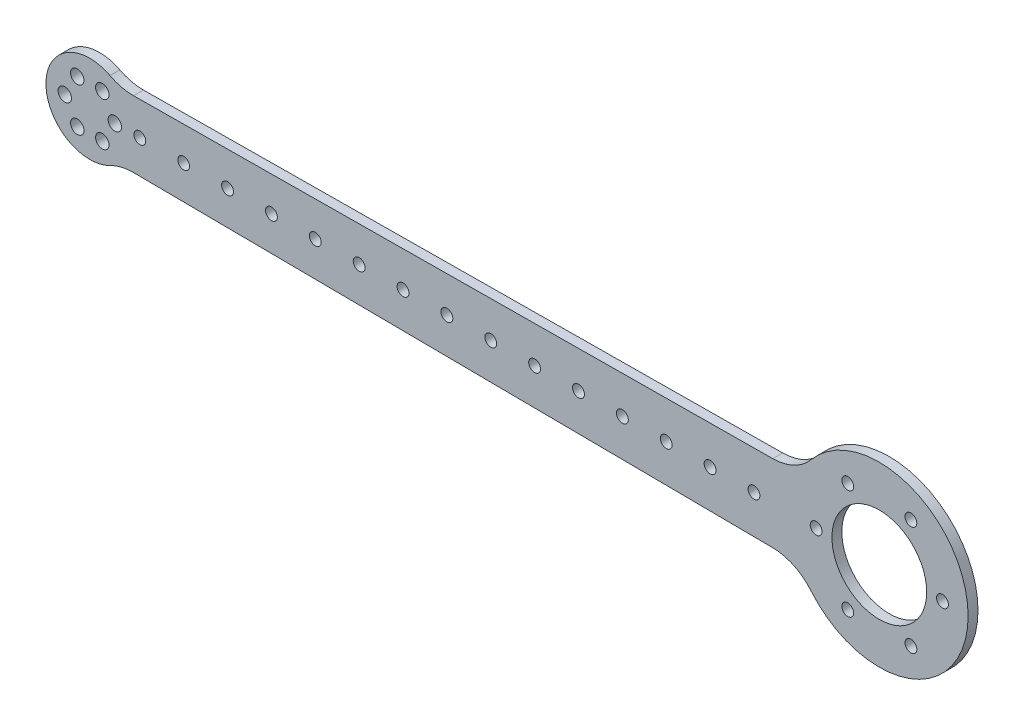
SolidWorks part; units mm, degrees
material "Hexcel AS4C (3000 Filaments)"
ref_plane "Front Plane" through (0, 0, 0) normal (0, 0, 1) x (1, 0, 0)
ref_plane "Top Plane" through (0, 0, 0) normal (0, 1, 0) x (1, 0, 0)
ref_plane "Right Plane" through (0, 0, 0) normal (1, 0, 0) x (0, 0, -1)
sketch "Sketch1" plane through (0, 0, 0) normal (0, 0, 1) x (1, 0, 0)
  line L0 (-100, 0) -> (100, 0) construction
  line L1 (-88.9892, 1.5) -> (77.6857, 2.8851)
  line L2 (-92.7234, 8.3988) -> (79.762, 9.8322)
  line L3 (-88.9892, -1.5) -> (77.6857, -2.8851)
  line L4 (-92.7234, -8.3988) -> (79.762, -9.8322)
  line L5 (-100, 0) -> (-100.0693, -8.3377) construction
  line L6 (-100.0693, -8.3377) -> (-92.7234, -8.3988) construction
  line L7 (-92.7234, 8.3988) -> (-100.0693, 8.3377) construction
  line L8 (-100.0693, 8.3377) -> (-100, 0) construction
  line L9 (-88.9892, 1.5) -> (-88.9892, -1.5)
  line L10 (100, 0) -> (99.9169, -9.9997) construction
  line L11 (99.9169, -9.9997) -> (79.762, -9.8322) construction
  line L12 (79.762, 9.8322) -> (99.9169, 9.9997) construction
  line L13 (99.9169, 9.9997) -> (100, 0) construction
  circle A0 centre (-100, 0) radius 11.1125 construction
  circle A1 centre (100, 0) radius 22.5 construction
  arc A2 (79.762, 9.8322) -> (79.762, -9.8322) centre (100, 0) cw
  arc A3 (77.6857, 2.8851) -> (77.6857, -2.8851) centre (100, 0) ccw
  arc A4 (-92.7234, 8.3988) -> (-92.7234, -8.3988) centre (-100, 0) ccw
  point P4 (0, 0)
  point P23 (-88.9892, 0)
  dimension "D2" = 22.225
  dimension "D3" = 45
  dimension "D1" = 200
  dimension "D5" = 6.9296
  dimension "D6" = 10
  dimension "D7" = 6.9296
  dimension "D4" = 10
  dimension "D8" = 3
extrude "Boss-Extrude1" add sketch "Sketch1" along normal mid plane 2.5
fillet "Fillet1" radius 12.7 4 edges at (79.762, 9.8322, 0) (79.762, -9.8322, 0) (-92.7234, -8.3988, 0) (-92.7234, 8.3988, 0)
sketch "Sketch2" plane through (0, 0, 0) normal (0, 0, 1) x (1, 0, 0)
  line L8 (-88.9892, 1.5) -> (-88.9892, -1.5) construction
  line L9 (-88.9892, -1.5) -> (77.6857, -2.8851) construction
  line L10 (77.6857, 2.8851) -> (-88.9892, 1.5) construction
  line L12 (-88.9892, 1.5) -> (-88.9892, -1.5)
  line L13 (-88.9892, -1.5) -> (77.6857, -2.8851)
  line L14 (77.6857, 2.8851) -> (-88.9892, 1.5)
  arc A6 (77.6857, 2.8851) -> (77.6857, -2.8851) centre (100, 0) ccw construction
  arc A7 (77.6857, 2.8851) -> (77.6857, -2.8851) centre (100, 0) ccw
extrude "Boss-Extrude2" add sketch "Sketch2" along normal mid plane 2.5
ref_axis "Axis1" through (100, 0, 1.25) along (0, 0, -1)
ref_axis "Axis2" through (-100, 0, 1.25) along (0, 0, -1)
sketch "Sketch3" plane through (0, 0, 0) normal (0, 0, 1) x (1, 0, 0)
  circle A0 centre (100, 0) radius 12
  dimension "D1" = 24
extrude "Cut-Extrude1" cut sketch "Sketch3" against normal through all both and the other way through all
sketch "Sketch5" plane through (0, 0, 0) normal (0, 0, 1) x (1, 0, 0)
  line L0 (100, 0) -> (116, 0) construction
  circle A0 centre (116, 0) radius 1.5
  dimension "D2" = 3
  dimension "D1" = 16
extrude "Cut-Extrude2" cut sketch "Sketch5" against normal through all both and the other way through all
pattern_circular "CirPattern1" count 6 over 360 about axis through (100, 0, 1.25) along (0, 0, -1) of "Cut-Extrude2"
sketch "Sketch6" plane through (0, 0, 1.25) normal (0, 0, 1) x (1, 0, 0)
  line L0 (100, 0) -> (68.25, 0) construction
  line L1 (-100, 0) -> (-31.7625, 0) construction
  circle A0 centre (68.25, 0) radius 1.5
  circle A1 centre (57.1375, 0) radius 1.5
  circle A2 centre (46.025, 0) radius 1.5
  circle A3 centre (34.9125, 0) radius 1.5
  circle A4 centre (23.8, 0) radius 1.5
  circle A5 centre (12.6875, 0) radius 1.5
  circle A6 centre (1.575, 0) radius 1.5
  circle A7 centre (-9.5375, 0) radius 1.5
  circle A8 centre (-20.65, 0) radius 1.5
  circle A9 centre (-31.7625, 0) radius 1.5
  circle A10 centre (-42.875, 0) radius 1.5
  circle A11 centre (-53.9875, 0) radius 1.5
  circle A12 centre (-65.1, 0) radius 1.5
  circle A13 centre (-76.2125, 0) radius 1.5
  circle A14 centre (-87.325, 0) radius 1.5
  dimension "D1" = 3
  dimension "D2" = 31.75
  dimension "D4" = 11.1125
  dimension "D3" = 15
extrude "Cut-Extrude3" cut sketch "Sketch6" against normal through all both and the other way through all
sketch "Sketch8" plane through (0, 0, 0) normal (0, 0, 1) x (1, 0, 0)
  line L1 (-115, -25.4) -> (-85, -25.4)
  line L2 (-115, -25.4) -> (-115, 25.4)
  line L3 (-115, 25.4) -> (-85, 25.4)
  line L4 (-85, -25.4) -> (-85, 25.4)
  line L5 (-115, -25.4) -> (-85, 25.4) construction
  line L6 (-115, 25.4) -> (-85, -25.4) construction
  point P0 (-100, 0)
  dimension "D1" = 15
  dimension "D2" = 50.8
extrude "Cut-Extrude4" [suppressed] cut sketch "Sketch8" against normal through all both and the other way through all
fillet "Fillet2" [suppressed] radius 2.3813
sketch "Sketch10" [suppressed] plane through (0, 0, 1.25) normal (0, 0, 1) x (1, 0, 0)
  line L0 (-100, 0) -> (-81.825, 0) construction
  line L1 (-85, -4.7688) -> (-85, 4.7688) construction
  line L2 (-81.825, -4) -> (-69.125, -4) construction
  line L3 (-81.825, -4) -> (-81.825, 4) construction
  line L4 (-81.825, 4) -> (-69.125, 4) construction
  line L5 (-69.125, -4) -> (-69.125, 4) construction
  circle A0 centre (-81.825, 4) radius 1.5
  circle A1 centre (-69.125, 4) radius 1.5
  circle A2 centre (-69.125, -4) radius 1.5
  circle A3 centre (-81.825, -4) radius 1.5
  point P8 (-81.825, 0)
  dimension "D4" = 3
  dimension "D1" = 3.175
  dimension "D2" = 12.7
  dimension "D3" = 8
extrude "Cut-Extrude5" [suppressed] cut sketch "Sketch10" against normal through all both and the other way through all
sketch "Sketch11" plane through (0, 0, 0) normal (0, 0, -1) x (-1, 0, 0)
  line L0 (93.65, 0) -> (100, 0) construction
  point P4 (93.65, 0)
  dimension "D2" = 6.35
hole_wizard "M3 Clearance Hole1" positions "Sketch12" profile "Sketch13" hole size "M3" standard "ANSI Metric" end condition up to next
sketch "Sketch12" plane through (0, 0, -1.25) normal (0, 0, -1) x (-1, 0, 0)
  point P0 (93.65, 0)
sketch "Sketch13" plane through (-93.65, 0, -1.25) normal (1, 0, 0) x (0, 1, 0)
  line L0 (0, 0) -> (0, 2.501)
  line L1 (0, 2.501) -> (1.7, 2.501)
  line L2 (1.7, 2.501) -> (1.7, 0)
  line L5 (1.7, 0) -> (0, 0)
  line L11 (0, -6.35) -> (0, 107.95) construction
  dimension "Thru Hole Dia." = 3.4
  dimension "Thru Hole Depth" = 2.501
pattern_circular "CirPattern3" count 6 over 360 about axis through (-100, 0, 1.25) along (0, 0, -1) of "M3 Clearance Hole1" reverse direction yes
equation "\"length\"= 200mm"
equation "\"D1@Sketch1\"=\"length\""
equation "\"Flange_Pulle\"= 45mm"
equation "\"D3@Sketch1\"=\"Flange_Pulle\""
equation "\"C_Upper\"= 10mm"
equation "\"Upper_Thickness\"= 5.5mm * ( 2 ^ ( 1 / 3 ) )"
equation "\"D5@Sketch1\"=\"Upper_Thickness\""
equation "\"C_Lower\"= 10mm"
equation "\"D6@Sketch1\"=\"C_Lower\""
equation "\"Lower_Thickness\"= \"Upper_Thickness\""
equation "\"D7@Sketch1\"=\"Lower_Thickness\""
equation "\"Foot_Diameter\"=0.875"
equation "\"D2@Sketch1\"=\"Foot_Diameter\""
equation "\"Thicknes\"= 2.5mm"
equation "\"D1@Boss-Extrude1\"=\"Thicknes\""
equation "\"D1@Boss-Extrude2\"=\"Thicknes\""
equation "\"D4@Sketch1\"=\"C_Upper\""
equation "\"m3_clearance\"= 3mm"
equation "\"screw_center_offset\"= 16mm"
equation "\"D2@Sketch5\"=\"m3_clearance\""
equation "\"D1@Sketch5\"=\"screw_center_offset\""
equation "\"D1@Sketch6\"=\"m3_clearance\""
equation "\"I_center_hole_spacing\"=0.4375"
equation "\"D4@Sketch6\"=\"I_center_hole_spacing\""
